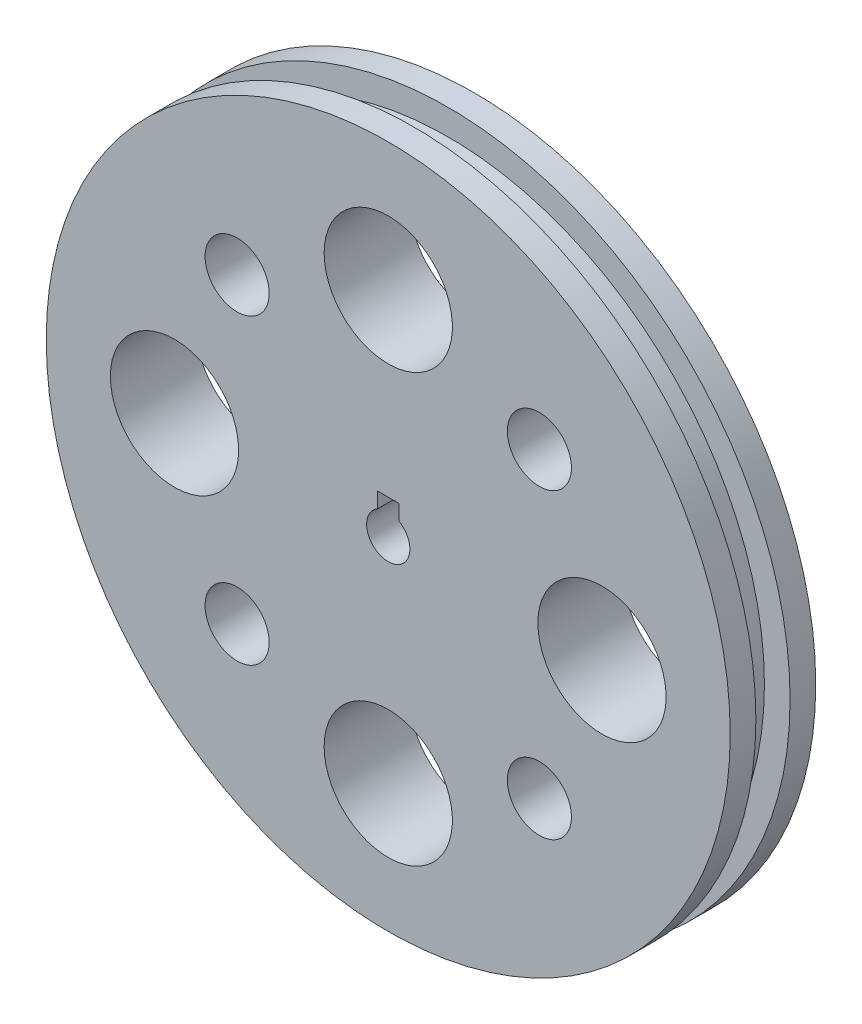
SolidWorks part; units mm, degrees
ref_plane "Front Plane" through (0, 0, 0) normal (0, 0, 1) x (1, 0, 0)
ref_plane "Top Plane" through (0, 0, 0) normal (0, 1, 0) x (1, 0, 0)
ref_plane "Right Plane" through (0, 0, 0) normal (1, 0, 0) x (0, 0, -1)
sketch "Sketch1" plane through (0, 0, 0) normal (0, 0, 1) x (1, 0, 0)
  circle A0 centre (0, 0) radius 101.6
  dimension "D1" = 203.2
extrude "Boss-Extrude1" add sketch "Sketch1" along normal blind 7.62
sketch "Sketch4" plane through (0, 0, 7.62) normal (0, 0, 1) x (1, 0, 0)
  circle A0 centre (0, 0) radius 93.98
  dimension "D1" = 187.96
extrude "Boss-Extrude2" add sketch "Sketch4" along normal blind 10.16
sketch "Sketch5" plane through (0, 0, 17.78) normal (0, 0, 1) x (1, 0, 0)
  circle A0 centre (0, 0) radius 101.6
  dimension "D1" = 203.2
extrude "Boss-Extrude3" add sketch "Sketch5" along normal blind 7.62
sketch "Sketch2" plane through (0, 0, 7.62) normal (0, 0, 1) x (1, 0, 0)
  line L0 (-101.6, 0) -> (101.6, 0) construction
  line L1 (0, 101.6) -> (0, -101.6) construction
  line L2 (0, 0) -> (-71.842, 71.842) construction
  circle A0 centre (0, 0) radius 101.6 construction
  circle A1 centre (-63.5, 0) radius 19.05
  circle A2 centre (-44.9013, 44.9013) radius 9.525
  circle A3 centre (0, 63.5) radius 19.05
  circle A4 centre (44.9013, 44.9013) radius 9.525
  circle A5 centre (63.5, 0) radius 19.05
  circle A6 centre (44.9013, -44.9013) radius 9.525
  circle A7 centre (0, -63.5) radius 19.05
  circle A8 centre (-44.9013, -44.9013) radius 9.525
  point P29 (0, 0)
  dimension "D1" = 38.1
  dimension "D4" = 19.05
  dimension "D5" = 63.5
  dimension "D2" = 63.5
  dimension "D3" = 45
  dimension "D6" = 4
extrude "Cut-Extrude1" cut sketch "Sketch2" against normal blind 25.4 and the other way through all
sketch "Sketch3" plane through (0, 0, 7.62) normal (0, 0, 1) x (1, 0, 0)
  line L2 (-3.175, 5.588) -> (-3.175, 10.16)
  line L3 (-3.175, 10.16) -> (3.175, 10.16)
  line L4 (3.175, 5.588) -> (3.175, 10.16)
  arc A0 (-3.175, 5.588) -> (3.175, 5.588) centre (0, 0) ccw
  dimension "D1" = 5.588
  dimension "D2" = 10.16
  dimension "D3" = 3.175
extrude "Cut-Extrude2" cut sketch "Sketch3" against normal blind 25.4
extrude "Cut-Extrude3" cut sketch "Sketch3<2>" along normal through all both and the other way through all
sketch "Sketch3<2>" plane through (0, 0, 7.62) normal (0, 0, 1) x (1, 0, 0) same geometry as "Sketch3"
